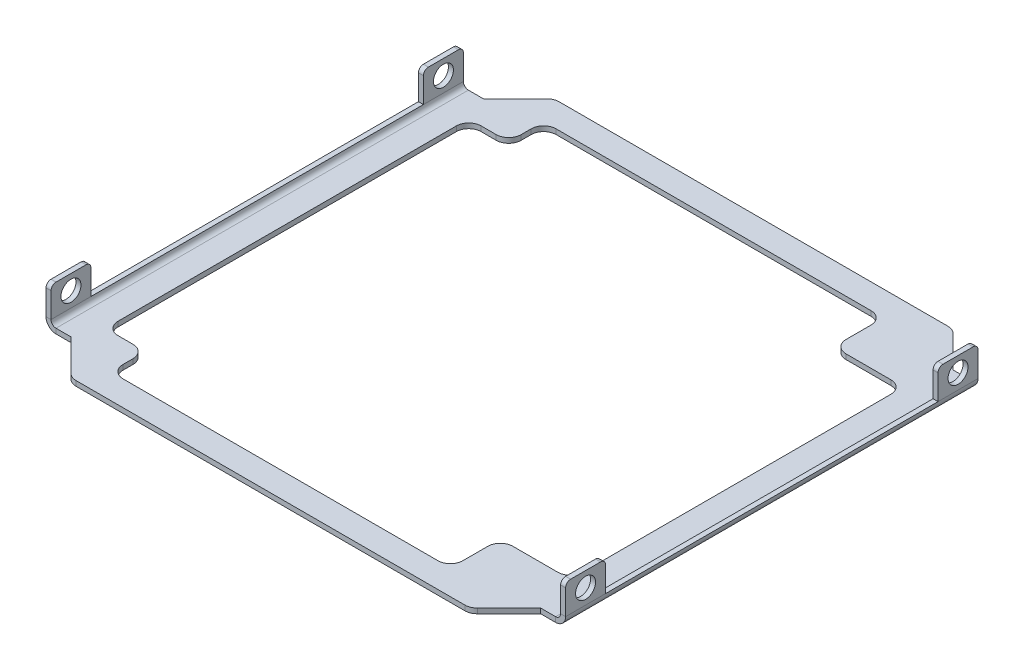
SolidWorks part; units mm, degrees
note: The reader was unsure of these and kept them because the rebuilt part matched: flange length of "Edge-Flange1".
material "6061-T6 (SS)"
ref_plane "Front Plane" through (0, 0, 0) normal (0, 0, 1) x (1, 0, 0)
ref_plane "Top Plane" through (0, 0, 0) normal (0, 1, 0) x (1, 0, 0)
ref_plane "Right Plane" through (0, 0, 0) normal (1, 0, 0) x (0, 0, -1)
sketch "Sketch1" plane through (0, 0, 0) normal (0, 1, 0) x (1, 0, 0)
  line L2 (0, 0) -> (0, 82.6)
  line L4 (104.072, 0) -> (104.072, 82.6)
  line L33 (104.072, 82.6) -> (99.072, 82.6)
  line L37 (5, 82.6) -> (0, 82.6)
  line L38 (5, 82.6) -> (12.0711, 89.6711)
  line L40 (92.0009, 89.6711) -> (99.072, 82.6)
  line L41 (0, 41.3) -> (104.072, 41.3) construction
  line L42 (92.0009, -7.0711) -> (99.072, 0)
  line L43 (12.0711, -7.0711) -> (92.0009, -7.0711)
  line L44 (5, 0) -> (12.0711, -7.0711)
  line L45 (5, 0) -> (0, 0)
  line L46 (104.072, 0) -> (99.072, 0)
  line L61 (92.0009, 89.6711) -> (12.0711, 89.6711)
  dimension "D1" = 82.6
  dimension "D2" = 104.072
  dimension "D3" = 5
  dimension "D4" = 79.9299
  dimension "D5" = 135
  dimension "D6" = 135
  dimension "D7" = 10
base flange "Base-Flange2" sketch "Sketch1" thickness 1 reverse thickness direction no parameters "D1"=1
edge flange "Edge-Flange1" sketch "Sketch14" flange profiles "Sketch14", "Sketch15" flange angle 90 flange length 8 flange position material inside bend radius 1 thickness 1 relief rectangular parameters "D6"=10, "D8"=1
sketch "Sketch14" plane through (104.072, 0, 0) normal (1, 0, 0) x (0, 0, -1)
  line L0 (0, 0) -> (82.6, 0) construction
  line L1 (0, 0) -> (82.6, 0)
  line L2 (0, 0) -> (0, 7)
  line L3 (0, 7) -> (82.6, 7)
  line L4 (82.6, 7) -> (82.6, 0)
  dimension "D1" = 7
sketch "Sketch15" plane through (0, 0, 0) normal (-1, 0, 0) x (0, 0, 1)
  line L0 (-82.6, 0) -> (0, 0) construction
  line L1 (-82.6, 0) -> (0, 0)
  line L2 (-82.6, 0) -> (-82.6, 7)
  line L3 (-82.6, 7) -> (0, 7)
  line L4 (0, 7) -> (0, 0)
  dimension "D1" = 7
bend "EdgeBend1" bend radius 1 bend angle 90 parameters "D5"=1
bend "EdgeBend2" bend radius 1 bend angle 90 parameters "D5"=2
sketch "Sketch16" plane through (104.072, 0, 0) normal (1, 0, 0) x (0, 0, -1)
  line L0 (82.6, 1) -> (0, 1) construction
  line L1 (8, 8) -> (74.6, 8)
  line L2 (8, 8) -> (8, 1)
  line L3 (8, 1) -> (74.6, 1)
  line L4 (74.6, 8) -> (74.6, 1)
  line L5 (0, 7) -> (0, 1) construction
  line L6 (82.6, 1) -> (82.6, 7) construction
  line L7 (82.6, 7) -> (0, 7) construction
  dimension "D1" = 8
  dimension "D2" = 8
  dimension "D3" = 1
extrude "Cut-Extrude1" cut sketch "Sketch16" against normal through all normal cut yes
fillet "Fillet1" radius 1 8 edges at (0.5, 7, -8) (0.5, 7, 0) (0.5, 7, -74.6) (0.5, 7, -82.6) (103.572, 7, -74.6) (103.572, 7, -82.6) (103.572, 7, 0) (103.572, 7, -8)
sketch "Sketch17" plane through (104.072, 0, 0) normal (1, 0, 0) x (0, 0, -1)
  line L0 (-7.0711, 0) -> (0, 0) construction
  line L1 (0, 6) -> (0, 1) construction
  line L2 (82.6, 0) -> (89.6711, 0) construction
  line L3 (82.6, 1) -> (82.6, 6) construction
  circle A0 centre (4, 4) radius 2
  circle A1 centre (78.6, 4) radius 2
  dimension "D1" = 4
  dimension "D4" = 4
  dimension "D2" = 4
  dimension "D3" = 4
  dimension "D5" = 4
  dimension "D6" = 4
extrude "Cut-Extrude2" cut sketch "Sketch17" against normal through all normal cut yes
sketch "Sketch19" plane through (0, 0, 0) normal (0, 1, 0) x (1, 0, 0)
  line L0 (15, -2.0711) -> (83.072, -2.0711)
  line L5 (12.0711, -7.0711) -> (92.0009, -7.0711) construction
  line L6 (92.0009, 89.6711) -> (12.0711, 89.6711) construction
  line L9 (7, 4.9289) -> (15, 4.9289)
  line L10 (15, -2.0711) -> (15, 4.9289)
  line L13 (7, 77.6711) -> (15, 77.6711)
  line L14 (15, 84.6711) -> (15, 77.6711)
  line L17 (97.072, 74.6711) -> (83.072, 74.6711)
  line L18 (83.072, 84.6711) -> (83.072, 74.6711)
  line L21 (97.072, 7.9289) -> (83.072, 7.9289)
  line L22 (83.072, -2.0711) -> (83.072, 7.9289)
  line L23 (97.072, 7.9289) -> (97.072, 74.6711)
  line L24 (83.072, 84.6711) -> (15, 84.6711)
  line L25 (7, 77.6711) -> (7, 4.9289)
  line L26 (2, 0) -> (2, 82.6) construction
  line L27 (102.072, 82.6) -> (102.072, 0) construction
  point P17 (0, 0)
  dimension "D1" = 5
  dimension "D2" = 5
  dimension "D3" = 5
  dimension "D4" = 5
  dimension "D5" = 14
  dimension "D6" = 8
  dimension "D7" = 15
  dimension "D8" = 12
extrude "Cut-Extrude3" cut sketch "Sketch19" against normal through all normal cut yes
fillet "Fillet2" radius 2.5 16 edges at (83.072, -0.5, 2.0711) (83.072, -0.5, -7.9289) (92.0009, -0.5, 7.0711) (97.072, -0.5, -7.9289) (97.072, -0.5, -74.6711) (83.072, -0.5, -74.6711) (83.072, -0.5, -84.6711) (92.0009, -0.5, -89.6711) (15, -0.5, -84.6711) (15, -0.5, -77.6711) (7, -0.5, -77.6711) (12.0711, -0.5, -89.6711) (12.0711, -0.5, 7.0711) (7, -0.5, -4.9289) (15, -0.5, 2.0711) (15, -0.5, -4.9289)
sketch "Bend-Lines3" [suppressed] plane through (0, 0, 0) normal (0, 1, 0) x (1, 0, 0)
sketch "Bounding-Box3" [suppressed] plane through (0, 0, 0) normal (0, 1, 0) x (1, 0, 0)
sheet metal parameters "Sheet-Metal2" thickness 1 parameters "D1"=1
flat pattern "Flat-Pattern2" [suppressed]
sketch "Bend-Lines4" plane through (0, 0, 0) normal (0, 1, 0) x (1, 0, 0)
sketch3d "Bounding-Box4" [suppressed]
  line L0 (-135.6338, 86.2583, 0) -> (0, 86.2583, 0) construction
  line L1 (-135.6338, 0, 0) -> (0, 0, 0) construction
  line L2 (-135.6338, 86.2583, 0) -> (-135.6338, 0, 0) construction
  line L3 (0, 86.2583, 0) -> (0, 0, 0) construction
sheet metal parameters "Sheet-Metal3" thickness 1 parameters "D1"=1
flat pattern "Flat-Pattern2"
sketch "Bend-Lines4" plane through (0, 0, 0) normal (0, 1, 0) x (1, 0, 0)
sketch3d "Bounding-Box4" [suppressed]
  line L0 (-135.6338, 86.2583, 0) -> (0, 86.2583, 0) construction
  line L1 (-135.6338, 0, 0) -> (0, 0, 0) construction
  line L2 (-135.6338, 86.2583, 0) -> (-135.6338, 0, 0) construction
  line L3 (0, 86.2583, 0) -> (0, 0, 0) construction
bend of the flat pattern "Flatten-<EdgeBend1>1"
bend of the flat pattern "Flatten-<EdgeBend2>1"
sheet metal parameters "Sheet-Metal4" thickness 1 parameters "D1"=1
flat pattern "Flat-Pattern2"
sketch "Bend-Lines4" plane through (0, 0, 0) normal (0, 1, 0) x (1, 0, 0)
sketch3d "Bounding-Box4" [suppressed]
  line L0 (-135.6338, 86.2583, 0) -> (0, 86.2583, 0) construction
  line L1 (-135.6338, 0, 0) -> (0, 0, 0) construction
  line L2 (-135.6338, 86.2583, 0) -> (-135.6338, 0, 0) construction
  line L3 (0, 86.2583, 0) -> (0, 0, 0) construction
bend of the flat pattern "Flatten-<EdgeBend1>1"
bend of the flat pattern "Flatten-<EdgeBend2>1"
sheet metal parameters "Sheet-Metal5" thickness 1 parameters "D1"=1
flat pattern "Flat-Pattern2"
sketch "Bend-Lines4" plane through (0, 0, 0) normal (0, 1, 0) x (1, 0, 0)
sketch3d "Bounding-Box4" [suppressed]
  line L0 (-135.6338, 86.2583, 0) -> (0, 86.2583, 0) construction
  line L1 (-135.6338, 0, 0) -> (0, 0, 0) construction
  line L2 (-135.6338, 86.2583, 0) -> (-135.6338, 0, 0) construction
  line L3 (0, 86.2583, 0) -> (0, 0, 0) construction
bend of the flat pattern "Flatten-<EdgeBend1>1"
bend of the flat pattern "Flatten-<EdgeBend2>1"
sheet metal parameters "Sheet-Metal7" thickness 1 parameters "D1"=1
flat pattern "Flat-Pattern2"
sketch "Bend-Lines4" plane through (0, 0, 0) normal (0, 1, 0) x (1, 0, 0)
sketch3d "Bounding-Box4" [suppressed]
  line L0 (-135.6338, 86.2583, 0) -> (0, 86.2583, 0) construction
  line L1 (-135.6338, 0, 0) -> (0, 0, 0) construction
  line L2 (-135.6338, 86.2583, 0) -> (-135.6338, 0, 0) construction
  line L3 (0, 86.2583, 0) -> (0, 0, 0) construction
bend of the flat pattern "Flatten-<EdgeBend1>1"
bend of the flat pattern "Flatten-<EdgeBend2>1"
